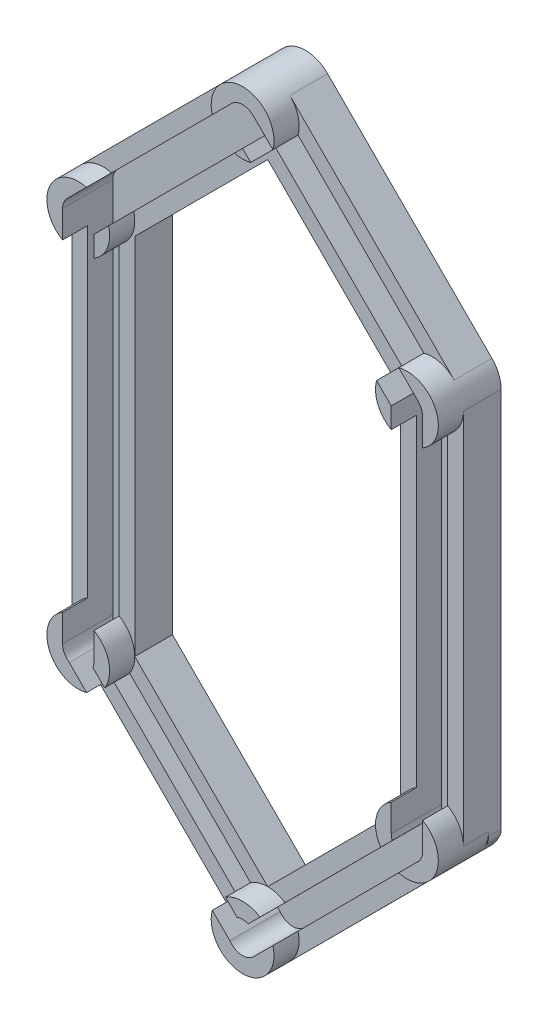
SolidWorks part; units mm, degrees
ref_plane "Спереди" through (0, 0, 0) normal (0, 0, 1) x (1, 0, 0)
ref_plane "Сверху" through (0, 0, 0) normal (0, 1, 0) x (1, 0, 0)
ref_plane "Справа" through (0, 0, 0) normal (1, 0, 0) x (0, 0, -1)
sketch "Эскиз1" plane through (0, 0, 0) normal (0, 0, 1) x (1, 0, 0)
  line L0 (-73.4107, 0) -> (65.3283, 0) construction
  line L1 (-12.0859, 4.2949) -> (-38.2489, -21.8681) construction
  line L2 (-12.0859, 4.2949) -> (14.077, -21.8681) construction
  line L3 (-38.2489, 0) -> (-38.2489, -121.4673) construction
  line L4 (14.077, 0) -> (14.077, -116.0096) construction
  line L5 (-38.2489, -81.8681) -> (14.077, -81.8681) construction
  line L6 (14.077, -81.8681) -> (-12.0859, -108.031) construction
  circle A0 centre (-12.0859, 4.2949) radius 2.5
  circle A1 centre (-12.0859, 4.2949) radius 5
  circle A2 centre (-38.2489, -21.8681) radius 2.5
  circle A3 centre (-38.2489, -21.8681) radius 5
  circle A4 centre (14.077, -21.8681) radius 2.5
  circle A5 centre (14.077, -21.8681) radius 5
  circle A6 centre (-38.2489, -81.8681) radius 2.5
  circle A7 centre (-38.2489, -81.8681) radius 5
  circle A8 centre (14.077, -81.8681) radius 2.5
  circle A9 centre (14.077, -81.8681) radius 5
  circle A10 centre (-12.0859, -108.031) radius 2.5
  circle A11 centre (-12.0859, -108.031) radius 5
  dimension "D2" = 5
  dimension "D3" = 10
  dimension "D5" = 45
  dimension "D1" = 45
  dimension "D4" = 37
  dimension "D6" = 37
  dimension "D7" = 60
  dimension "D8" = 60
  dimension "D9" = 37
  dimension "D10" = 45
  dimension "D11" = 37
extrude "Бобышка-Вытянуть1" add sketch "Эскиз1" along normal blind 10
sketch "Эскиз3" plane through (0, 0, 0) normal (0, 0, -1) x (-1, 0, 0)
  line L0 (12.0859, 4.2949) -> (15.6215, 7.8304)
  line L1 (15.6215, 7.8304) -> (41.7844, -18.3326)
  line L2 (41.7844, -18.3326) -> (34.7133, -25.4036)
  line L3 (34.7133, -25.4036) -> (8.5504, 0.7593)
  line L4 (8.5504, 0.7593) -> (12.0859, 4.2949)
  circle A0 centre (12.0859, 4.2949) radius 5 construction
  circle A1 centre (38.2489, -21.8681) radius 5 construction
extrude "Бобышка-Вытянуть2" add sketch "Эскиз3" against normal blind 6
sketch "Эскиз4" plane through (0, 0, 6) normal (0, 0, 1) x (1, 0, 0)
  line L0 (-13.8537, 6.0626) -> (-10.3181, 2.5271)
  line L1 (-13.8537, 6.0626) -> (-10.3181, 2.5271) construction
  line L2 (-10.3181, 2.5271) -> (-36.4811, -23.6359)
  line L3 (-36.4811, -23.6359) -> (-40.0166, -20.1003) construction
  line L4 (-36.4811, -23.6359) -> (-40.0166, -20.1003)
  line L5 (-40.0166, -20.1003) -> (-13.8537, 6.0626)
  line L6 (-8.5504, 0.7593) -> (-34.7133, -25.4036) construction
  line L8 (-41.7844, -18.3326) -> (-15.6215, 7.8304) construction
  dimension "D1" = 2.5
  dimension "D2" = 2.5
sketch "Эскиз9" plane through (0, 0, 0) normal (0, 0, -1) x (-1, 0, 0)
  line L0 (-14.077, -21.8681) -> (-17.6126, -18.3326)
  line L1 (-17.6126, -18.3326) -> (8.5504, 7.8304)
  line L2 (8.5504, 7.8304) -> (15.6215, 0.7593)
  line L3 (15.6215, 0.7593) -> (-10.5415, -25.4036)
  line L4 (-10.5415, -25.4036) -> (-14.077, -21.8681)
  circle A0 centre (-14.077, -21.8681) radius 5 construction
  arc A1 (15.6215, 7.8304) -> (8.5504, 0.7593) centre (12.0859, 4.2949) ccw construction
extrude "Бобышка-Вытянуть4" add sketch "Эскиз9" against normal blind 6
extrude "Вырез-Вытянуть1" cut sketch "Эскиз4" against normal blind 4
sketch "Эскиз5" plane through (0, 0, 0) normal (0, 0, -1) x (-1, 0, 0)
  line L0 (13.8537, 6.0626) -> (12.0859, 4.2949) construction
  line L1 (36.4811, -23.6359) -> (40.0166, -20.1003) construction
  circle A0 centre (12.9698, 5.1787) radius 3.75
  circle A1 centre (38.2489, -21.8681) radius 2.5
  arc A2 (36.4811, -23.6359) -> (40.0166, -20.1003) centre (38.2489, -21.8681) ccw construction
  arc A3 (13.8537, 6.0626) -> (10.3181, 6.0626) centre (12.0859, 4.2949) ccw construction
extrude "Бобышка-Вытянуть3" add sketch "Эскиз5" against normal blind 2
extrude "Вырез-Вытянуть2" cut sketch "Эскиз4<2>" along normal blind 4
sketch "Эскиз4<2>" plane through (0, 0, 6) normal (0, 0, 1) x (1, 0, 0) same geometry as "Эскиз4"
sketch "Эскиз10" plane through (0, 0, 10) normal (0, 0, 1) x (1, 0, 0)
  line L0 (14.077, -21.8681) -> (12.3093, -23.6359)
  line L1 (12.3093, -23.6359) -> (-13.8537, 2.5271)
  line L2 (-13.8537, 2.5271) -> (-12.0859, 4.2949)
  line L3 (-12.0859, 4.2949) -> (-10.3181, 6.0626)
  line L4 (-10.3181, 6.0626) -> (15.8448, -20.1003)
  line L5 (15.8448, -20.1003) -> (14.077, -21.8681)
  circle A0 centre (14.077, -21.8681) radius 2.5 construction
  arc A1 (-10.3181, 2.5271) -> (-13.8537, 6.0626) centre (-12.0859, 4.2949) ccw construction
extrude "Вырез-Вытянуть3" cut sketch "Эскиз10" against normal blind 8
sketch "Эскиз11" plane through (0, 0, 0) normal (0, 0, -1) x (-1, 0, 0)
  line L0 (-15.8448, -20.1003) -> (-12.3093, -23.6359) construction
  circle A0 centre (-14.077, -21.8681) radius 2.5
  arc A1 (-15.8448, -20.1003) -> (-12.3093, -23.6359) centre (-14.077, -21.8681) ccw construction
extrude "Бобышка-Вытянуть9" add sketch "Эскиз11" against normal blind 2
sketch "Skizze2" plane through (0, 0, 0) normal (0, 0, -1) x (-1, 0, 0)
  line L0 (-19.077, -21.8681) -> (-19.077, -82.5099)
  line L1 (-18.6013, -83.9967) -> (-17.9635, -85.0138)
  line L2 (-17.9635, -85.0138) -> (8.5478, -111.564)
  line L3 (8.5478, -111.564) -> (15.6241, -111.564)
  line L4 (15.6241, -111.564) -> (41.7844, -85.4037)
  line L5 (41.7844, -85.4037) -> (43.2489, -81.8681)
  line L6 (43.2489, -81.8681) -> (43.2489, -21.8681)
  line L7 (33.2489, -81.8681) -> (33.2489, -23.9392)
  line L8 (12.0859, -2.7762) -> (34.7133, -25.4036) construction
  line L9 (33.2489, -23.9392) -> (43.2489, -21.8681)
  line L10 (33.2489, -81.8681) -> (12.0859, -103.031)
  line L11 (12.0859, -103.031) -> (-9.077, -81.8681)
  line L12 (-9.077, -81.8681) -> (-9.077, -23.9392)
  line L13 (-10.5415, -25.4036) -> (12.0859, -2.7762) construction
  line L14 (-9.077, -23.9392) -> (-19.077, -21.8681)
  arc A0 (-17.6126, -18.3326) -> (-10.5415, -25.4036) centre (-14.077, -21.8681) ccw construction
  arc A1 (-19.077, -82.5099) -> (-18.6013, -83.9967) centre (-16.5158, -82.5099) ccw
  circle A2 centre (-14.077, -81.8681) radius 5 construction
  circle A3 centre (12.0859, -108.031) radius 5 construction
  circle A4 centre (38.2489, -81.8681) radius 5 construction
  arc A5 (34.7133, -25.4036) -> (41.7844, -18.3326) centre (38.2489, -21.8681) ccw construction
extrude "Aufsatz-Linear austragen1" add sketch "Skizze2" against normal blind 6
sketch "Skizze4" plane through (0, 0, 10) normal (0, 0, 1) x (1, 0, 0)
  line L0 (11.577, -22.0611) -> (16.577, -22.0611)
  line L1 (16.577, -22.0611) -> (16.577, -81.8681)
  line L2 (16.577, -81.8681) -> (11.577, -81.8681)
  line L3 (11.577, -81.8681) -> (11.577, -22.0611)
  circle A0 centre (14.077, -81.8681) radius 2.5 construction
  circle A1 centre (14.077, -81.8681) radius 2.5 construction
  point P9 (11.4025, -21.9517)
extrude "Schnitt-Linear austragen1" cut sketch "Skizze4" against normal blind 8
sketch "Skizze5" plane through (0, 0, 10) normal (0, 0, 1) x (1, 0, 0)
  line L0 (-38.2489, -81.8681) -> (-35.7489, -81.8681)
  line L1 (-35.7489, -81.8681) -> (-35.7489, -21.8681)
  line L2 (-38.2489, -81.8681) -> (-40.7489, -81.8681)
  line L3 (-40.7489, -81.8681) -> (-40.7489, -21.8681)
  line L4 (-40.7489, -21.8681) -> (-35.7489, -21.8681)
  circle A0 centre (-38.2489, -81.8681) radius 2.5 construction
  arc A1 (-40.0166, -20.1003) -> (-40.6921, -22.3976) centre (-38.2489, -21.8681) ccw construction
  point P5 (0, 0)
extrude "Schnitt-Linear austragen2" cut sketch "Skizze5" against normal blind 8
sketch "Skizze6" plane through (0, 0, 10) normal (0, 0, 1) x (1, 0, 0)
  line L0 (-12.8158, -107.3468) -> (13.706, -80.7861)
  line L2 (13.706, -80.7861) -> (16.1827, -83.2591)
  line L3 (16.1827, -83.2591) -> (-10.3391, -109.8198)
  line L5 (-10.3391, -109.8198) -> (-12.8158, -107.3468)
  line L6 (17.2285, -85.7499) -> (-8.5478, -111.564) construction
  dimension "D1" = 2.5
  dimension "D2" = 3.5
extrude "Schnitt-Linear austragen3" cut sketch "Skizze6" against normal blind 8
sketch "Skizze8" plane through (0, 0, 10) normal (0, 0, 1) x (1, 0, 0)
  line L0 (-37.3688, -81.2837) -> (-11.1862, -107.4663)
  line L1 (-11.1862, -107.4663) -> (-13.6611, -109.9412)
  line L2 (-13.6611, -109.9412) -> (-39.8437, -83.7585)
  line L3 (-39.8437, -83.7585) -> (-37.3688, -81.2837)
  line L5 (-33.2489, -81.8681) -> (-12.0859, -103.031) construction
  dimension "D1" = 2.5
  dimension "D2" = 3.5
extrude "Schnitt-Linear austragen6" cut sketch "Skizze8" against normal blind 8
sketch "Skizze10" plane through (0, 0, 6) normal (0, 0, 1) x (1, 0, 0)
  line L1 (19.077, -82.5099) -> (19.077, -81.8681)
  line L2 (-12.9627, -105.6898) -> (-12.0613, -106.5912)
  line L3 (-11.9406, -108.2207) -> (-13.6611, -109.9412)
  line L4 (-13.6611, -109.9412) -> (-14.1255, -109.4767)
  line L5 (-10.3393, -109.8197) -> (-11.9406, -108.2207)
  line L6 (-11.9406, -108.2207) -> (-13.6611, -109.9412)
  line L7 (-13.6611, -109.9412) -> (-14.1255, -109.4767)
  line L8 (-10.3393, -109.8197) -> (-11.9406, -108.2207)
  line L9 (-12.0613, -106.5912) -> (-11.1745, -105.7031)
  line L10 (-12.9627, -105.6898) -> (-12.0613, -106.5912)
  line L11 (-12.0613, -106.5912) -> (-11.1745, -105.7031)
  line L12 (-36.7844, -81.8681) -> (-35.9076, -82.7448)
  line L13 (-39.8437, -83.7585) -> (-37.9533, -81.8681)
  line L14 (-37.9533, -81.8681) -> (-40.7489, -81.8681)
  line L15 (-39.6945, -83.9077) -> (-39.8437, -83.7585)
  line L16 (-39.8437, -83.7585) -> (-37.9533, -81.8681)
  line L17 (-37.9533, -81.8681) -> (-40.7489, -81.8681)
  line L18 (-39.6945, -83.9077) -> (-39.8437, -83.7585)
  line L19 (-35.7489, -81.8681) -> (-36.7844, -81.8681)
  line L20 (-36.7844, -81.8681) -> (-35.9076, -82.7448)
  line L21 (-35.7489, -81.8681) -> (-36.7844, -81.8681)
  line L22 (14.7896, -81.8681) -> (16.1656, -83.2421)
  line L23 (16.577, -81.8681) -> (14.7896, -81.8681)
  line L24 (14.7896, -81.8681) -> (16.1656, -83.2421)
  line L25 (16.577, -81.8681) -> (14.7896, -81.8681)
  line L26 (11.7397, -82.7552) -> (12.6255, -81.8681)
  line L27 (12.6255, -81.8681) -> (11.577, -81.8681)
  line L28 (11.7397, -82.7552) -> (12.6255, -81.8681)
  line L29 (12.6255, -81.8681) -> (11.577, -81.8681)
  line L30 (19.077, -82.5099) -> (19.077, -81.8681)
  arc A1 (-14.1255, -109.4767) -> (-10.3393, -109.8197) centre (-12.0859, -108.031) ccw
  arc A2 (-14.1255, -109.4767) -> (-10.3393, -109.8197) centre (-12.0859, -108.031) ccw
  arc A3 (-11.1745, -105.7031) -> (-12.9627, -105.6898) centre (-12.0859, -108.031) ccw
  arc A4 (-11.1745, -105.7031) -> (-12.9627, -105.6898) centre (-12.0859, -108.031) ccw
  arc A5 (-40.7489, -81.8681) -> (-39.6945, -83.9077) centre (-38.2489, -81.8681) ccw
  arc A6 (-40.7489, -81.8681) -> (-39.6945, -83.9077) centre (-38.2489, -81.8681) ccw
  arc A7 (-35.9076, -82.7448) -> (-35.7489, -81.8681) centre (-38.2489, -81.8681) ccw
  arc A8 (-35.9076, -82.7448) -> (-35.7489, -81.8681) centre (-38.2489, -81.8681) ccw
  arc A9 (16.1656, -83.2421) -> (16.577, -81.8681) centre (14.077, -81.8681) ccw
  arc A10 (16.1656, -83.2421) -> (16.577, -81.8681) centre (14.077, -81.8681) ccw
  arc A11 (11.577, -81.8681) -> (11.7397, -82.7552) centre (14.077, -81.8681) ccw
  arc A12 (11.577, -81.8681) -> (11.7397, -82.7552) centre (14.077, -81.8681) ccw
  arc A14 (18.6013, -83.9967) -> (19.077, -81.8681) centre (14.077, -81.8681) ccw
  arc A15 (18.6013, -83.9967) -> (19.077, -82.5099) centre (16.5158, -82.5099) ccw
  arc A16 (18.6013, -83.9967) -> (19.077, -81.8681) centre (14.077, -81.8681) ccw
  arc A17 (18.6013, -83.9967) -> (19.077, -82.5099) centre (16.5158, -82.5099) ccw
  dimension "D1" = 0
  dimension "D2" = 0
  dimension "D3" = 0
  dimension "D4" = 0
  dimension "D5" = 0
  dimension "D6" = 0
  dimension "D7" = 0
extrude "Schnitt-Linear austragen7" cut sketch "Skizze10" against normal blind 4
